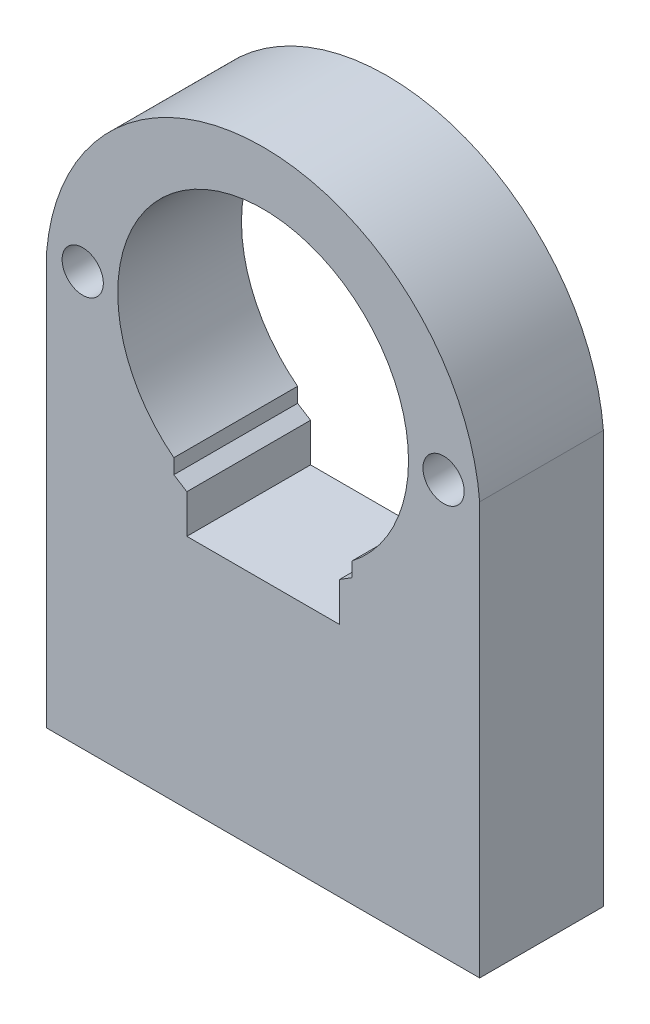
SolidWorks part; units mm, degrees
ref_plane "Front Plane" through (0, 0, 0) normal (0, 0, 1) x (1, 0, 0)
ref_plane "Top Plane" through (0, 0, 0) normal (0, 1, 0) x (1, 0, 0)
ref_plane "Right Plane" through (0, 0, 0) normal (1, 0, 0) x (0, 0, -1)
sketch "Sketch1" plane through (0, 0, 0) normal (0, 0, 1) x (1, 0, 0)
  line L0 (-21, 10.349) -> (-21, -29.651)
  line L1 (-21, -29.651) -> (21, -29.651)
  line L2 (21, -29.651) -> (21, 10.349)
  line L3 (-7.4, -1.653) -> (-7.4, -6.751)
  line L4 (-7.4, -6.751) -> (7.4, -6.751)
  line L5 (7.4, -6.751) -> (7.4, -1.653)
  arc A0 (-21, 10.349) -> (21, 10.349) centre (0, 8.5763) cw
  arc A1 (-13.6327, 13.949) -> (-13.6327, 6.749) centre (0, 10.349) ccw
  arc A2 (13.6327, 13.949) -> (13.6327, 6.749) centre (0, 10.349) cw
  arc A3 (7.4, -1.653) -> (13.6327, 6.749) centre (0, 10.349) ccw
  arc A4 (13.6327, 13.949) -> (-13.6327, 13.949) centre (0, 10.349) ccw
  arc A5 (-13.6327, 6.749) -> (-7.4, -1.653) centre (0, 10.349) ccw
  dimension "D1" = 40
extrude "Boss-Extrude1" add sketch "Sketch1" along normal blind 12
sketch "Sketch4" plane through (0, 0, 0) normal (0, 0, -1) x (-1, 0, 0)
  line L0 (-8.6089, -0.7561) -> (-8.6089, -2.2205)
  line L1 (-8.6089, -2.2205) -> (-7.3901, -2.9852)
  line L2 (-7.3901, -2.9852) -> (-7.3901, -1.635)
  line L3 (-7.3901, -1.635) -> (-8.6089, -0.7561)
  line L4 (7.3804, -3.0137) -> (7.3804, -1.6593)
  line L5 (8.6603, -2.2107) -> (7.3804, -3.0137)
  line L6 (8.6603, -0.6984) -> (8.6603, -2.2107)
  line L7 (7.3804, -1.6593) -> (8.6603, -0.6984)
  point P8 (-8.592, -0.7683)
  point P9 (8.6116, -0.7349)
extrude "Cut-Extrude1" cut sketch "Sketch4" against normal through all
sketch "Sketch5" plane through (0, 0, 0) normal (0, 0, -1) x (-1, 0, 0)
  line L0 (0, 0) -> (0, 35.9723) construction
  circle A0 centre (-17.5, 10.449) radius 2
  arc A1 (8.6603, -0.7779) -> (-8.6089, -0.8177) centre (0, 10.349) ccw construction
  circle A2 centre (17.5, 10.449) radius 2
  point P8 (-0.0325, 24.449)
  dimension "D1" = 4
  dimension "D2" = 14
  dimension "D3" = 35
extrude "Cut-Extrude2" cut sketch "Sketch5" against normal through all
